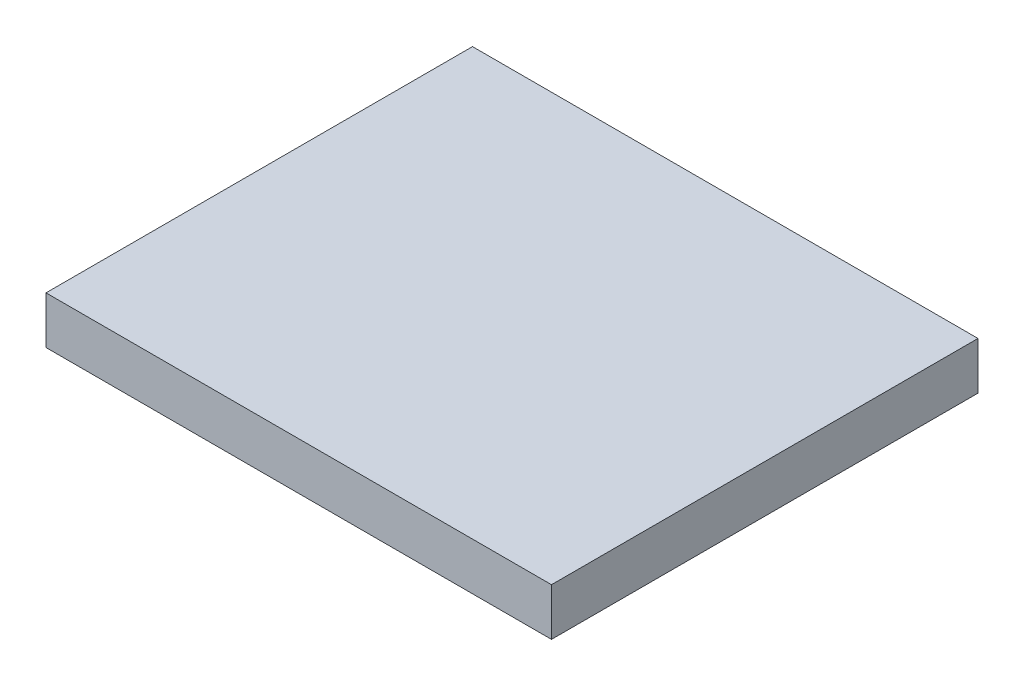
SolidWorks part; units mm, degrees
ref_plane "Front Plane" through (0, 0, 0) normal (0, 0, 1) x (1, 0, 0)
ref_plane "Top Plane" through (0, 0, 0) normal (0, 1, 0) x (1, 0, 0)
ref_plane "Right Plane" through (0, 0, 0) normal (1, 0, 0) x (0, 0, -1)
sketch "Sketch1" plane through (0, 0, 0) normal (0, 1, 0) x (1, 0, 0)
  line L1 (-48.635, 59.4953) -> (154.565, 59.4953)
  line L2 (-48.635, 59.4953) -> (-48.635, -111.9547)
  line L3 (-48.635, -111.9547) -> (154.565, -111.9547)
  line L4 (154.565, 59.4953) -> (154.565, -111.9547)
  line L5 (-48.635, 59.4953) -> (154.565, -111.9547) construction
  line L6 (-48.635, -111.9547) -> (154.565, 59.4953) construction
  point P0 (52.965, -26.2297)
extrude "Boss-Extrude1" add sketch "Sketch1" along normal blind 19.05 contours L2 L1 L4 L3
